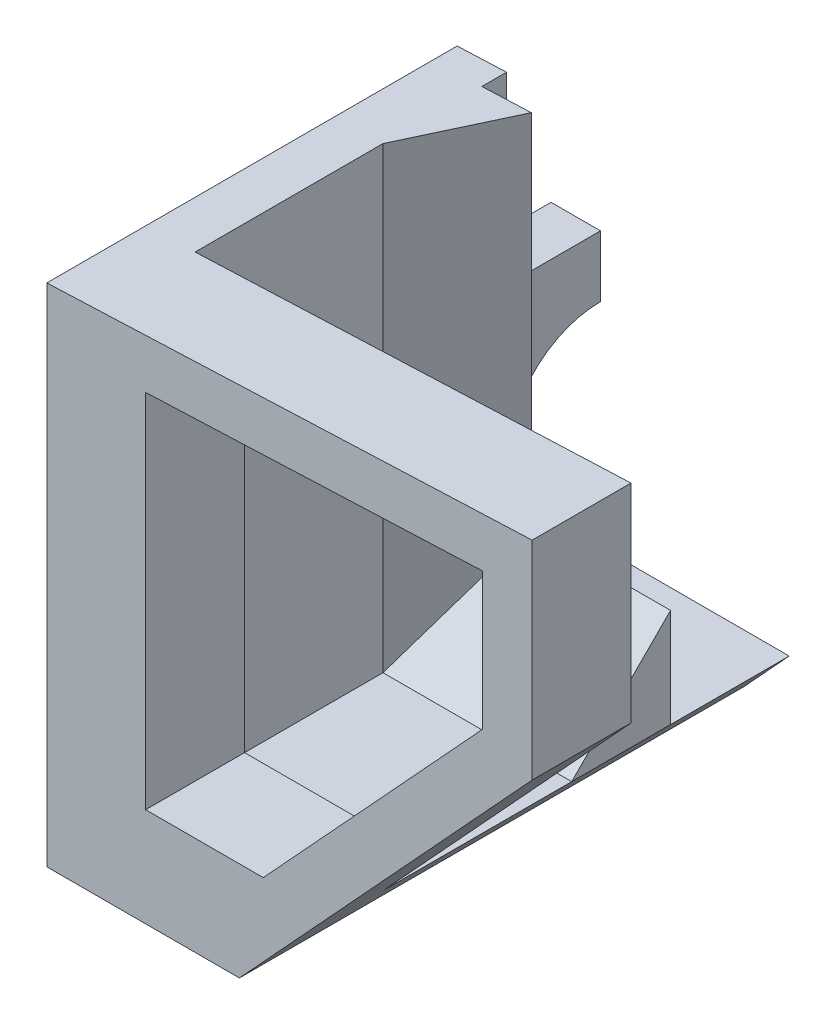
SolidWorks part; units mm, degrees
note: The reader was unsure of these and kept them because the rebuilt part matched: shared geometry of "Sketch2<5>".
ref_plane "Front Plane" through (0, 0, 0) normal (0, 0, 1) x (1, 0, 0)
ref_plane "Top Plane" through (0, 0, 0) normal (0, 1, 0) x (1, 0, 0)
ref_plane "Right Plane" through (0, 0, 0) normal (1, 0, 0) x (0, 0, -1)
sketch "Sketch2" plane through (0, 0, 0) normal (0, 0, 1) x (1, 0, 0)
  line L2 (-5, -51.3446) -> (-5, -0.2052)
  line L4 (0, 0) -> (0, -46.3446) construction
  line L8 (44.0837, -19.205) -> (44.0837, 1.809)
  line L9 (-5, -51.3446) -> (14.4779, -51.3446)
  line L11 (44.0837, 1.809) -> (-5, -0.2052)
  line L13 (19.0837, -46.3446) -> (0, -46.3446)
  line L18 (44.0837, -19.205) -> (14.4779, -51.3446)
  point P0 (0, 0)
  dimension "D2" = 46.3446
  dimension "D3" = 2.35
  dimension "D4" = 19.0837
  dimension "D5" = 45
  dimension "D8" = 5
  dimension "D9" = 5
  dimension "D12" = 25
extrude "Boss-Extrude1" add sketch "Sketch2" along normal blind 10 contours L9 L18 L8 L11 L2
extrude "Boss-Extrude6" add sketch "Sketch2<5>" against normal blind 41
sketch "Sketch2<5>" plane through (0, 0, 0) normal (0, 0, 1) x (1, 0, 0) same geometry as "Sketch2"
sketch "Sketch6" plane through (0, 0, 0) normal (1, 0, 0) x (0, 0, -1)
  line L0 (41, 0) -> (41, -46.3446) construction
  line L1 (41, -46.3446) -> (0, -46.3446) construction
  line L2 (41, 0) -> (0, 0) construction
  line L5 (41, -17.1446) -> (33, -17.1446) construction
  line L6 (33, 0) -> (33, -17.1446) construction
  line L7 (41, -18.6446) -> (31.5, -18.6446)
  line L8 (31.5, 0) -> (31.5, -18.6446)
  line L9 (31.5, 0) -> (41, 0)
  line L10 (41, 0) -> (41, -18.6446)
  circle A0 centre (41, -34.3446) radius 8 construction
  circle A1 centre (41, -34.3446) radius 9.5
  point P13 (41, -26.3446)
  dimension "D2" = 16
  dimension "D1" = 12
  dimension "D4" = 9.2
  dimension "D5" = 8
extrude "Cut-Extrude1" cut sketch "Sketch6" against normal up to next
sketch "Sketch7" plane through (0, 0, 0) normal (0, 0, -1) x (-1, 0, 0)
  line L10 (-39.0837, -17.2531) -> (-16.8915, -41.3446)
  line L11 (-16.8915, -41.3446) -> (-5, -41.3446)
  line L12 (-5, -41.3446) -> (-5, -4.799)
  line L13 (-5, -4.799) -> (-39.0837, -3.4004)
  line L14 (-39.0837, -3.4004) -> (-39.0837, -17.2531)
  line L15 (-39.0837, -17.2531) -> (-16.8915, -41.3446)
  line L17 (-5, -41.3446) -> (-5, -4.799)
  line L18 (-5, -4.799) -> (-39.0837, -3.4004)
  line L19 (-39.0837, -3.4004) -> (-39.0837, -17.2531)
  line L22 (-16.8915, -41.3446) -> (-5, -41.3446)
  dimension "D1" = 5
extrude "Cut-Extrude2" cut sketch "Sketch7" against normal up to next
ref_plane "Plane1" through (0, 0, -29) normal (0, 0, 1) x (1, 0, 0)
sketch "Sketch10" plane through (0, 0, -29) normal (0, 0, 1) x (1, 0, 0)
  line L0 (19.0837, -46.3446) -> (0, -46.3446) construction
  line L1 (19.0837, -46.3446) -> (0, -46.3446)
  line L2 (0, 0) -> (0, -46.3446) construction
  line L3 (0, 0) -> (0, -46.3446)
  line L4 (19.0837, -46.3446) -> (19.0837, -36.3446)
  line L5 (19.0837, -36.3446) -> (5, -36.3446)
  line L6 (5, -36.3446) -> (5, 0.2052)
  line L7 (0, 0) -> (5, 0.2052)
  line L8 (44.0837, 1.809) -> (0, 0) construction
  dimension "D1" = 10
  dimension "D2" = 5
extrude "Boss-Extrude9" add sketch "Sketch10" along normal blind 10
chamfer "Chamfer2" distance 10 distance2 5 1 edges at (5, -18.0697, -19)
chamfer "Chamfer3" distance 10 angle 45 1 edges at (9.5419, -36.3446, -19)
